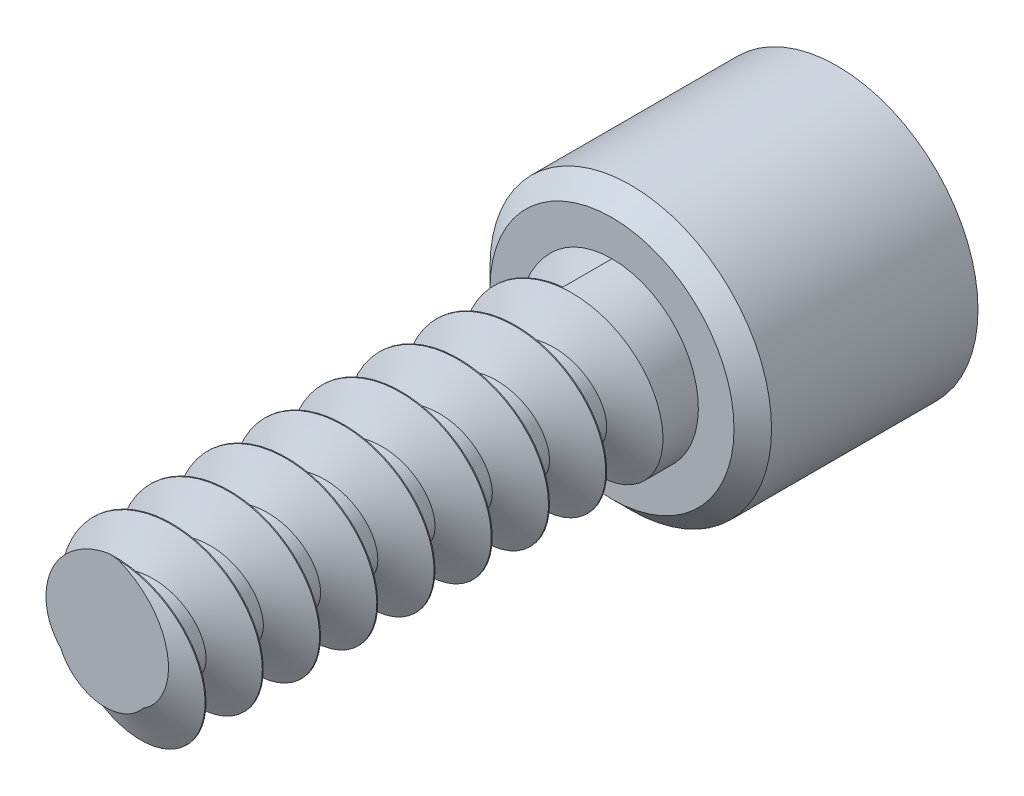
SolidWorks part; units mm, degrees
ref_plane "Front Plane" through (0, 0, 0) normal (0, 0, 1) x (1, 0, 0)
ref_plane "Top Plane" through (0, 0, 0) normal (0, 1, 0) x (1, 0, 0)
ref_plane "Right Plane" through (0, 0, 0) normal (1, 0, 0) x (0, 0, -1)
sketch "Sketch1" plane through (0, 0, 0) normal (0, 0, 1) x (1, 0, 0)
  circle A0 centre (-12.7526, 7.5681) radius 7.5
extrude "Boss-Extrude1" add sketch "Sketch1" along normal blind 12
sketch "Sketch4" plane through (0, 0, 12) normal (0, 0, 1) x (1, 0, 0)
  circle A0 centre (-12.7526, 7.5681) radius 4.6
  circle A1 centre (-12.7526, 7.5681) radius 7.5 construction
extrude "Boss-Extrude2" add sketch "Sketch4" along normal blind 27
sketch "Sketch7" plane through (0, 0, 39) normal (0, 0, 1) x (1, 0, 0)
  circle A0 centre (-12.7526, 7.5681) radius 4.6
  circle A1 centre (-12.7526, 7.5681) radius 4.6 construction
sketch3d "3DSketch4"
  line L0 (-12.5518, 12.1637, 39) -> (-12.5518, 12.1637, 36)
  line L2 (-12.5518, 12.1637, 39) -> (-12.5518, 10.1593, 38)
  line L3 (-12.5518, 10.1593, 38) -> (-12.5518, 10.1593, 37)
  line L4 (-12.5518, 10.1593, 37) -> (-12.5518, 12.1637, 36)
  circle A4 centre (-12.7526, 7.5681, 39) radius 4.6 construction
  point P4 (-12.7526, 7.5681, 43.6)
  dimension "D1" = 2.24
  dimension "D2" = 2.24
  dimension "D3" = 1
  dimension "D4" = 3
curve "Helix/Spiral2" pitch 3.05 height 24.4 turns 8
sweep "Cut-Sweep9" cut profiles "3DSketch4" path "Helix/Spiral2"
chamfer "Chamfer1" distance 1 angle 45 1 edges at (-5.2526, 7.5681, 12)
sketch "Sketch12" plane through (0, 0, 0) normal (0, 0, -1) x (-1, 0, 0)
  line L0 (15.7013, 7.5681) -> (9.8682, 7.5681) construction
  line L1 (16.7526, 6.8181) -> (16.7526, 8.3181)
  line L2 (16.7526, 8.3181) -> (8.7526, 8.3181)
  line L3 (8.7526, 8.3181) -> (8.7526, 6.8181)
  line L4 (16.7526, 6.8181) -> (8.7526, 6.8181)
  point P8 (8.7526, 7.5681)
  point P9 (16.7526, 7.5681)
  dimension "D1" = 1.5
  dimension "D2" = 4
  dimension "D3" = 4
extrude "Cut-Extrude1" cut sketch "Sketch12" against normal blind 8
